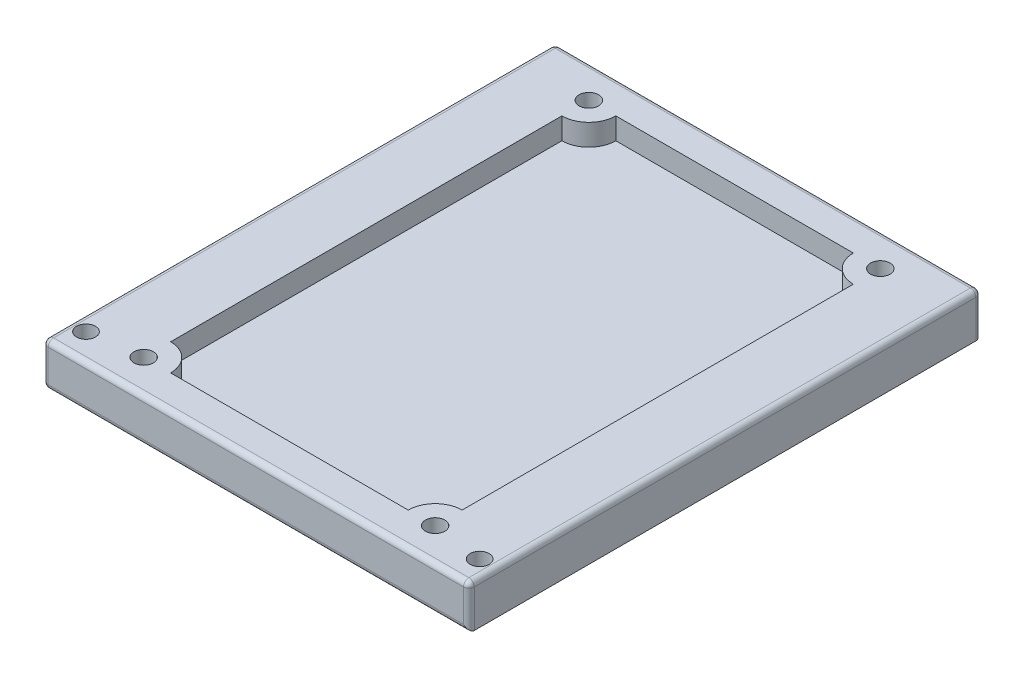
SolidWorks part; units mm, degrees
ref_plane "Front Plane" through (0, 0, 0) normal (0, 0, 1) x (1, 0, 0)
ref_plane "Top Plane" through (0, 0, 0) normal (0, 1, 0) x (1, 0, 0)
ref_plane "Right Plane" through (0, 0, 0) normal (1, 0, 0) x (0, 0, -1)
sketch "Sketch1" plane through (0, 0, 0) normal (0, 1, 0) x (1, 0, 0)
  line L0 (39.5, 95) -> (39.5, 0) construction
  line L1 (0, 0) -> (79, 0)
  line L2 (0, 0) -> (0, 95)
  line L3 (0, 95) -> (79, 95)
  line L4 (79, 0) -> (79, 95)
  circle A0 centre (3, 5) radius 1.75
  circle A1 centre (12.475, 6.225) radius 1.65 construction
  circle A2 centre (12.475, 88.775) radius 1.65 construction
  circle A3 centre (76, 5) radius 1.75
  circle A4 centre (66.525, 6.225) radius 1.65 construction
  circle A5 centre (66.525, 88.775) radius 1.65 construction
  dimension "D2" = 3
  dimension "D3" = 3.5
  dimension "D5" = 5
  dimension "D6" = 12.475
  dimension "D7" = 3.3
  dimension "D8" = 12.475
  dimension "D9" = 82.55
  dimension "D10" = 3.3
  dimension "D11" = 6.225
  dimension "D1" = 79
  dimension "D4" = 95
extrude "Boss-Extrude1" add sketch "Sketch1" along normal blind 8
sketch "Sketch3" plane through (0, 0, 0) normal (0, -1, 0) x (1, 0, 0)
  point P0 (12.475, -6.225)
  point P1 (66.525, -6.225)
  point P3 (66.525, -88.775)
  point P5 (12.475, -88.775)
hole_wizard "CBORE for M3 SHCS1" positions "Sketch3" profile "Sketch4" counterbore size "M3" standard "ANSI Metric" end condition through all
sketch "Sketch4" plane through (12.475, 0, -6.225) normal (1, 0, 0) x (0, 0, -1)
  line L0 (0, 0) -> (0, 8)
  line L1 (0, 8) -> (1.8, 8)
  line L3 (1.8, 8) -> (1.8, 3)
  line L4 (1.8, 3) -> (3.25, 3)
  line L5 (3.25, 3) -> (3.25, 0)
  line L7 (3.25, 0) -> (0, 0)
  line L11 (0, -6.35) -> (0, 107.95) construction
  dimension "Thru Hole Dia." = 3.6
  dimension "Thru Hole Depth" = 8
  dimension "C'Bore Dia." = 6.5
  dimension "C'Bore Depth" = 3
sketch "Sketch5" plane through (0, 8, 0) normal (0, 1, 0) x (1, 0, 0)
  line L1 (17.475, 88.775) -> (61.525, 88.775)
  line L2 (12.475, 83.775) -> (12.475, 11.225)
  line L3 (17.475, 6.225) -> (61.525, 6.225)
  line L4 (66.525, 83.775) -> (66.525, 11.225)
  circle A0 centre (12.475, 88.775) radius 1.65 construction
  circle A1 centre (12.475, 6.225) radius 1.65 construction
  arc A3 (12.475, 83.775) -> (17.475, 88.775) centre (12.475, 88.775) ccw
  arc A4 (61.525, 88.775) -> (66.525, 83.775) centre (66.525, 88.775) ccw
  arc A5 (66.525, 11.225) -> (61.525, 6.225) centre (66.525, 6.225) ccw
  arc A6 (17.475, 6.225) -> (12.475, 11.225) centre (12.475, 6.225) ccw
  point P12 (0, 0)
  dimension "D3" = 54.05
  dimension "D1" = 0
  dimension "D2" = 0
extrude "Cut-Extrude1" cut sketch "Sketch5" against normal blind 4
sketch "Sketch6" plane through (0, 0, 0) normal (0, -1, 0) x (1, 0, 0)
  line L1 (9.475, -30) -> (14.475, -30)
  line L2 (9.475, -30) -> (9.475, -50)
  line L3 (9.475, -50) -> (14.475, -50)
  line L4 (14.475, -30) -> (14.475, -50)
  dimension "D1" = 5
  dimension "D2" = 20
  dimension "D3" = 3
  dimension "D4" = 25
extrude "Boss-Extrude2" add sketch "Sketch6" along normal blind 8.8
sketch "Sketch7" plane through (0, 0, -50) normal (0, 0, -1) x (-1, 0, 0)
  line L0 (-14.475, -8.8) -> (-14.475, 0) construction
  line L1 (-9.475, 0) -> (-12.675, 0)
  line L2 (-9.475, 0) -> (-9.475, -6.8)
  line L3 (-9.475, -6.8) -> (-12.675, -6.8)
  line L4 (-12.675, 0) -> (-12.675, -6.8)
  dimension "D1" = 6.8
  dimension "D2" = 1.8
extrude "Cut-Extrude2" cut sketch "Sketch7" against normal through all
fillet "Fillet1" radius 6 1 edges at (14.475, 0, -40) second distance 8 first distance on face at (12.475, 0, -9.475)
fillet "Fillet2" radius 1 10 edges at (0, 4, 0) (39.5, 8, 0) (79, 4, 0) (79, 4, -95) (79, 8, -47.5) (39.5, 8, -95) (0, 4, -95) (0, 8, -47.5) (0, 0, -47.5) (39.5, 0, 0)
